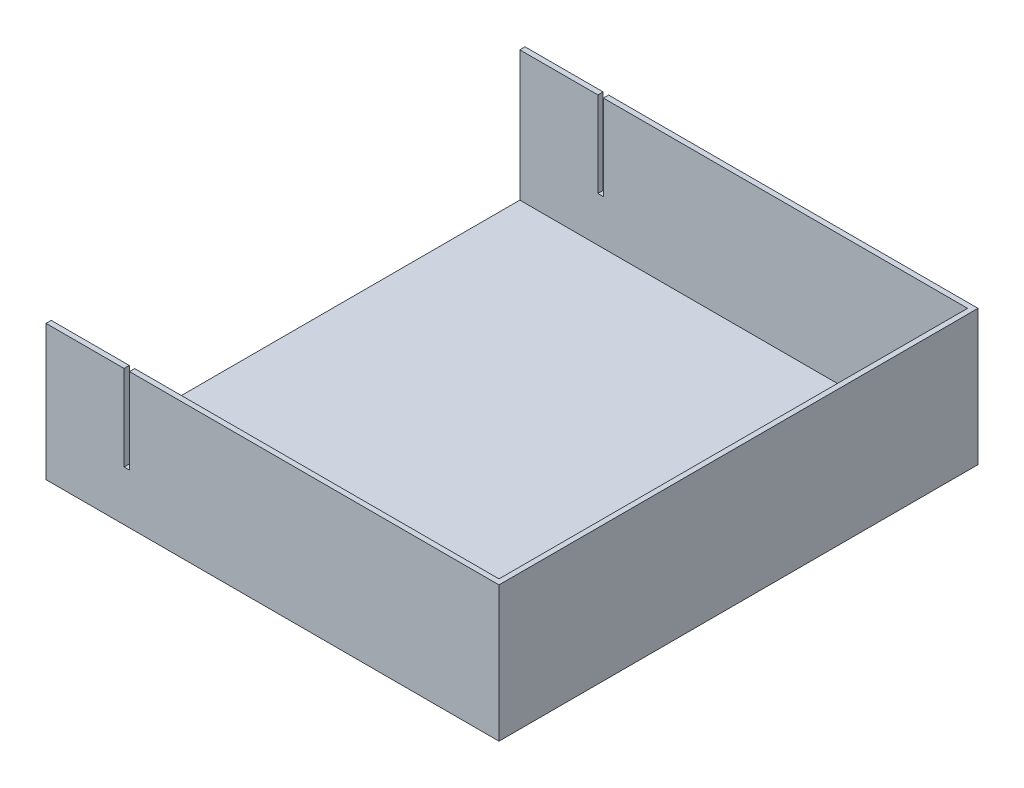
SolidWorks part; units mm, degrees
ref_plane "Front Plane" through (0, 0, 0) normal (0, 0, 1) x (1, 0, 0)
ref_plane "Top Plane" through (0, 0, 0) normal (0, 1, 0) x (1, 0, 0)
ref_plane "Right Plane" through (0, 0, 0) normal (1, 0, 0) x (0, 0, -1)
sketch "Sketch1" plane through (0, 0, 0) normal (0, 1, 0) x (1, 0, 0)
  line L1 (0, 0) -> (279.4, 0)
  line L2 (0, 0) -> (0, 292.1)
  line L3 (0, 292.1) -> (279.4, 292.1)
  line L4 (279.4, 0) -> (279.4, 292.1)
  dimension "D1" = 279.4
  dimension "D2" = 292.1
extrude "Boss-Extrude1" add sketch "Sketch1" along normal blind 82.55
sketch "Sketch3" plane through (0, 82.55, 0) normal (0, 1, 0) x (1, 0, 0)
  line L14 (3.175, 3.175) -> (276.225, 3.175)
  line L15 (276.225, 3.175) -> (276.225, 288.925)
  line L16 (3.175, 288.925) -> (3.175, 3.175)
  line L17 (276.225, 288.925) -> (3.175, 288.925)
  line L18 (3.175, 3.175) -> (276.225, 3.175)
  line L19 (276.225, 3.175) -> (276.225, 288.925)
  line L20 (3.175, 288.925) -> (3.175, 3.175)
  line L21 (276.225, 288.925) -> (3.175, 288.925)
  dimension "D1" = 3.175
extrude "Cut-Extrude1" cut sketch "Sketch3" against normal blind 79.375
sketch "Sketch4" plane through (0, 82.55, 0) normal (0, 1, 0) x (1, 0, 0)
  line L0 (279.4, 292.1) -> (0, 292.1) construction
  line L6 (3.175, 288.925) -> (3.175, 3.175) construction
  line L7 (0, 0) -> (3.175, 0)
  line L8 (0, 0) -> (0, 292.1)
  line L9 (0, 292.1) -> (3.175, 292.1)
  line L10 (3.175, 0) -> (3.175, 292.1)
extrude "Cut-Extrude2" cut sketch "Sketch4" against normal up to next
sketch "Sketch5" plane through (0, 0, -292.1) normal (0, 0, -1) x (-1, 0, 0)
  line L1 (-50.8, 82.55) -> (-54.102, 82.55)
  line L2 (-50.8, 82.55) -> (-50.8, 30.48)
  line L3 (-50.8, 30.48) -> (-54.102, 30.48)
  line L4 (-279.4, 0) -> (-3.175, 0)
  line L5 (-3.175, 0) -> (-3.175, 82.55)
  line L6 (-3.175, 82.55) -> (-279.4, 82.55)
  line L7 (-279.4, 82.55) -> (-279.4, 0)
  line L8 (-279.4, 0) -> (-3.175, 0)
  line L9 (-3.175, 0) -> (-3.175, 82.55)
  line L10 (-3.175, 82.55) -> (-279.4, 82.55)
  line L11 (-279.4, 82.55) -> (-279.4, 0)
  line L12 (-54.102, 82.55) -> (-54.102, 30.48)
  line M11 (-3.175, 82.55) -> (-279.4, 82.55)
  dimension "D2" = 3.302
  dimension "D3" = 52.07
  dimension "D4" = 47.625
  dimension "D1" = 0
extrude "Cut-Extrude3" cut sketch "Sketch5" against normal through all contours L12 L3 L2 M11 region at (52.451, 56.515, -292.1)
